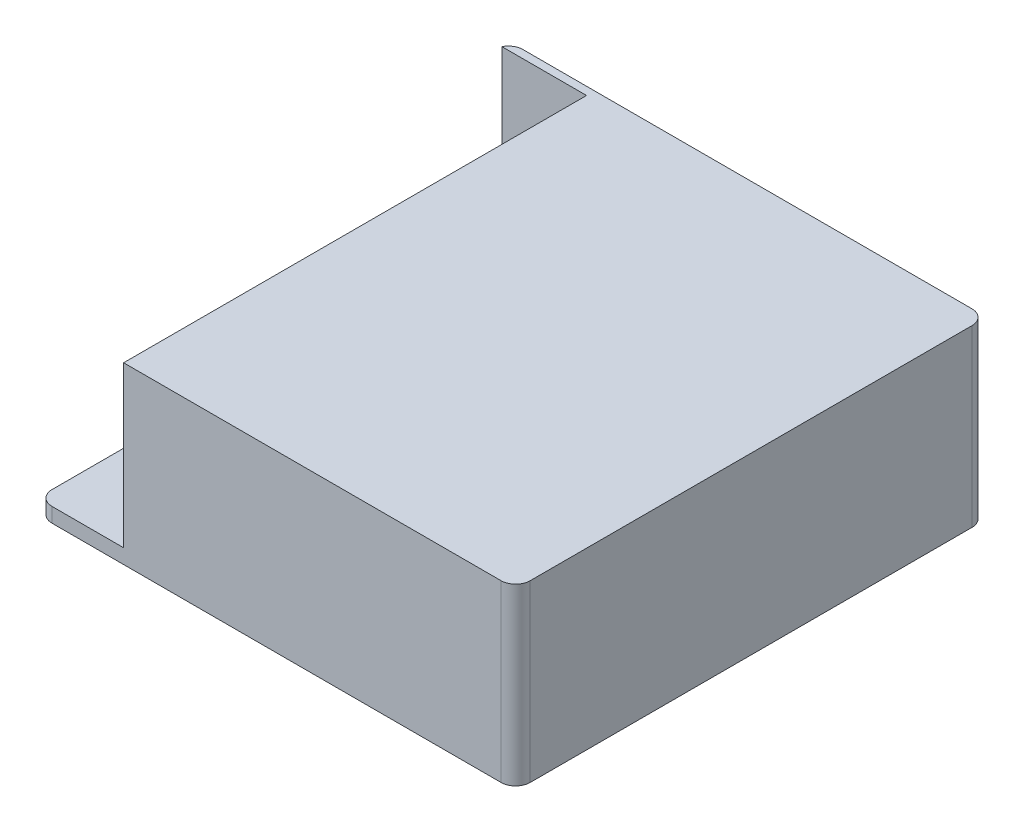
SolidWorks part; units mm, degrees
ref_plane "Front Plane" through (0, 0, 0) normal (0, 0, 1) x (1, 0, 0)
ref_plane "Top Plane" through (0, 0, 0) normal (0, 1, 0) x (1, 0, 0)
ref_plane "Right Plane" through (0, 0, 0) normal (1, 0, 0) x (0, 0, -1)
sketch "Sketch1" plane through (0, 0, 0) normal (0, 1, 0) x (1, 0, 0)
  line L1 (-46.25, 48.5) -> (46.25, 48.5)
  line L2 (-49.25, 45.5) -> (-49.25, -45.5)
  line L3 (-46.25, -48.5) -> (46.25, -48.5)
  line L4 (49.25, 45.5) -> (49.25, -45.5)
  line L5 (-49.25, 48.5) -> (49.25, -48.5) construction
  line L6 (-49.25, -48.5) -> (49.25, 48.5) construction
  arc A0 (49.25, -45.5) -> (46.25, -48.5) centre (46.25, -45.5) cw
  arc A1 (49.25, 45.5) -> (46.25, 48.5) centre (46.25, 45.5) ccw
  arc A2 (-49.25, 45.5) -> (-46.25, 48.5) centre (-46.25, 45.5) cw
  arc A3 (-49.25, -45.5) -> (-46.25, -48.5) centre (-46.25, -45.5) ccw
  point P0 (0, 0)
  dimension "D1" = 3
extrude "Boss-Extrude1" add sketch "Sketch1" along normal blind 36
sketch "Sketch2" plane through (0, 36, 0) normal (0, 1, 0) x (1, 0, 0)
  line L1 (-56.5894, 46.8529) -> (-31.4967, 46.8529)
  line L2 (-56.5894, 46.8529) -> (-56.5894, -51.1657)
  line L3 (-56.5894, -51.1657) -> (-31.4967, -51.1657)
  line L4 (-31.4967, 46.8529) -> (-31.4967, -51.1657)
extrude "Cut-Extrude1" cut sketch "Sketch2" against normal blind 33
sketch "Sketch3" plane through (0, 3, 0) normal (0, 1, 0) x (1, 0, 0)
  line L0 (-49.25, 45.5) -> (-49.25, -45.5) construction
  line L1 (-49.25, 37.7045) -> (-31.4967, 37.7045)
  line L2 (-49.25, 37.7045) -> (-49.25, -20.5839)
  line L3 (-49.25, -20.5839) -> (-31.4967, -20.5839)
  line L4 (-31.4967, 37.7045) -> (-31.4967, -20.5839)
  line L5 (-31.4967, 46.8529) -> (-31.4967, -48.5) construction
extrude "Boss-Extrude2" add sketch "Sketch3" along normal blind 12 separate body
sketch "Sketch4" plane through (0, 0, 0) normal (0, -1, 0) x (1, 0, 0)
  line L0 (0, -3) -> (-68.1762, -3) construction
  line L1 (-46.25, 48.5) -> (46.25, 48.5) construction
  line L2 (-49.25, -45.5) -> (-49.25, 45.5) construction
  circle A0 centre (-28.75, -3) radius 1.5
  circle A1 centre (26.25, -3) radius 1.5
  dimension "D2" = 20.5
  dimension "D3" = 55
  dimension "D1" = 51.5
extrude "Cut-Extrude2" cut sketch "Sketch4" against normal blind 5
